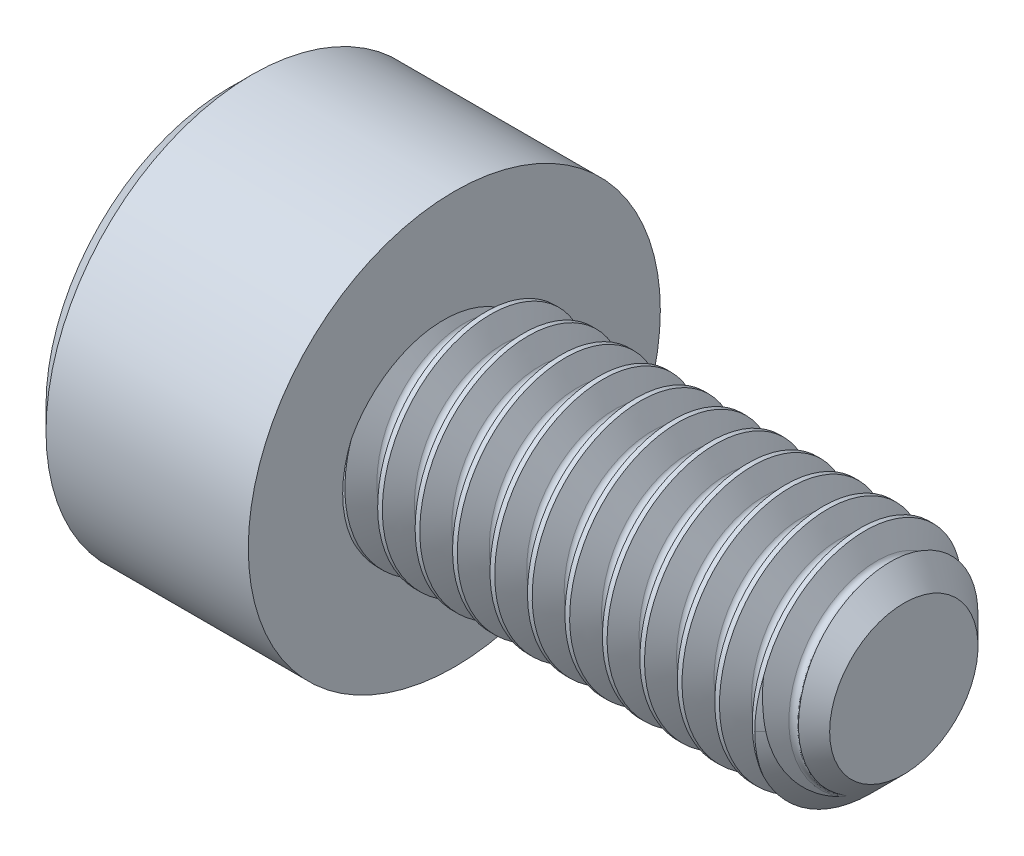
SolidWorks part; units mm, degrees
material "AISI Type 316L stainless steel"
ref_plane "Front Plane" through (0, 0, 0) normal (0, 0, 1) x (1, 0, 0)
ref_plane "Top Plane" through (0, 0, 0) normal (0, 1, 0) x (1, 0, 0)
ref_plane "Right Plane" through (0, 0, 0) normal (1, 0, 0) x (0, 0, -1)
sketch "Sketch1" plane through (0, 0, 0) normal (0, 0, 1) x (1, 0, 0)
  line L0 (-88.7055, 0) -> (96.9812, 0) construction
  line L1 (0, 0) -> (0, 2.75)
  line L2 (0, 2.75) -> (3, 2.75)
  line L4 (9, 0) -> (9, 1.49)
  line L5 (9, 1.49) -> (3, 1.49)
  line L6 (3, 1.49) -> (3, 2.75)
  line L7 (0, 0) -> (9, 0)
revolve "Revolve1" add sketch "Sketch1" angle 360 about L0 other way angle 360
chamfer "Chamfer1" distance 0.5 angle 45 1 edges at (9, 0, 1.49)
chamfer "Chamfer2" distance 0.3 angle 45 1 edges at (0, 0, 2.75)
sketch "Sketch3" plane through (0, 0, 0) normal (1, 0, 0) x (0, 0, -1)
  line L1 (-1.4434, 0) -> (-0.7217, -1.25)
  line L2 (-0.7217, -1.25) -> (0.7217, -1.25)
  line L3 (0.7217, -1.25) -> (1.4434, 0)
  line L4 (1.4434, 0) -> (0.7217, 1.25)
  line L5 (0.7217, 1.25) -> (-0.7217, 1.25)
  line L6 (-0.7217, 1.25) -> (-1.4434, 0)
  circle A0 centre (0, 0) radius 1.25 construction
extrude "Cut-Extrude1" cut sketch "Sketch3" along normal blind 2.5
chamfer "Chamfer3" distance 0.3 angle 45 6 edges at (0, 1.25, 0) (0, 0.625, 1.0825) (0, -0.625, 1.0825) (0, -1.25, 0) (0, -0.625, -1.0825) (0, 0.625, -1.0825)
sketch "Sketch5" plane through (9, 0, 0) normal (1, 0, 0) x (0, 0, -1)
  circle A0 centre (0, 0) radius 1.49
curve "Helix/Spiral1" pitch 0.5 height 6 radius 1.49 centre (9, 0, 0) axis (-1, 0, 0) start towards (0, 0, -1)
sketch "Sketch8" plane through (0, 0, 0) normal (0, 1, 0) x (1, 0, 0)
  line L0 (9, 1.49) -> (9, 1.1111) construction
  line L1 (9.0625, 1.2194) -> (9.3281, 1.6794)
  line L2 (9.3281, 1.6794) -> (8.6719, 1.6794)
  line L3 (8.6719, 1.6794) -> (8.9375, 1.2194)
  line L4 (9, -0.99) -> (9, 0.99) construction
  circle A0 centre (9, 1.49) radius 0.1894 construction
  arc A1 (9.0625, 1.2194) -> (8.9375, 1.2194) centre (9, 1.2555) cw
  dimension "D2" = 0.0722
  dimension "D1" = 0.3789
sweep "Cut-Sweep1" cut profiles "Sketch8" path "Helix/Spiral1" align with end faces yes
